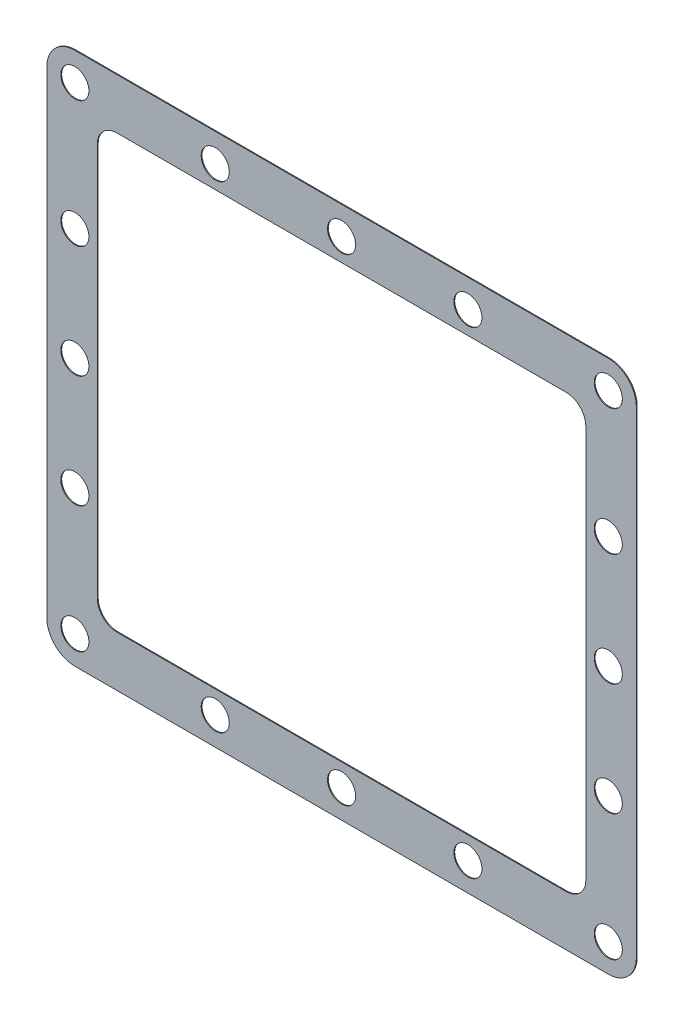
SolidWorks part; units mm, degrees
ref_plane "前视基准面" through (0, 0, 0) normal (0, 0, 1) x (1, 0, 0)
ref_plane "上视基准面" through (0, 0, 0) normal (0, 1, 0) x (1, 0, 0)
ref_plane "右视基准面" through (0, 0, 0) normal (1, 0, 0) x (0, 0, -1)
sketch "草图1" plane through (0, 0, 0) normal (0, 0, 1) x (1, 0, 0)
  line L0 (95, -85) -> (95, 85) construction
  line L1 (-95, -95) -> (95, -95)
  line L2 (-105, -85) -> (-105, 85)
  line L3 (-95, 95) -> (95, 95)
  line L4 (105, -85) -> (105, 85)
  line L5 (-105, -95) -> (105, 95) construction
  line L6 (-105, 95) -> (105, -95) construction
  line L7 (-80, -77) -> (80, -77)
  line L8 (-87, -70) -> (-87, 70)
  line L9 (-80, 77) -> (80, 77)
  line L10 (87, -70) -> (87, 70)
  line L11 (-87, -77) -> (87, 77) construction
  line L12 (-87, 77) -> (87, -77) construction
  line L13 (0, 0) -> (0, 37.6622) construction
  line L14 (0, 0) -> (41.7484, 0) construction
  line L15 (-95, 85) -> (95, 85) construction
  line L16 (-95, -85) -> (95, -85) construction
  arc A0 (95, 95) -> (105, 85) centre (95, 85) cw
  arc A1 (95, -95) -> (105, -85) centre (95, -85) ccw
  arc A2 (-95, -95) -> (-105, -85) centre (-95, -85) cw
  arc A3 (-105, 85) -> (-95, 95) centre (-95, 85) cw
  arc A4 (80, 77) -> (87, 70) centre (80, 70) cw
  arc A5 (80, -77) -> (87, -70) centre (80, -70) ccw
  arc A6 (-80, -77) -> (-87, -70) centre (-80, -70) cw
  arc A7 (-87, 70) -> (-80, 77) centre (-80, 70) cw
  circle A8 centre (95, -85) radius 5
  circle A9 centre (95, 85) radius 5
  circle A10 centre (-95, 85) radius 5
  circle A11 centre (-95, -85) radius 5
  circle A12 centre (95, 0) radius 5
  circle A13 centre (95, -40) radius 5
  circle A14 centre (95, 40) radius 5
  circle A15 centre (-95, -40) radius 5
  circle A16 centre (-95, 0) radius 5
  circle A17 centre (-95, 40) radius 5
  circle A18 centre (0, 85) radius 5
  circle A19 centre (-45, 85) radius 5
  circle A20 centre (45, 85) radius 5
  circle A21 centre (0, -85) radius 5
  circle A22 centre (-45, -85) radius 5
  circle A23 centre (45, -85) radius 5
  point P0 (0, 0)
  point P18 (0, 0)
  dimension "D3" = 10
  dimension "D6" = 7
  dimension "D7" = 10
  dimension "D8" = 10
  dimension "D9" = 10
  dimension "D10" = 10
  dimension "D11" = 10
  dimension "D12" = 10
  dimension "D13" = 10
  dimension "D14" = 40
  dimension "D15" = 40
  dimension "D16" = 10
  dimension "D17" = 10
  dimension "D18" = 10
  dimension "D19" = 45
  dimension "D20" = 45
  dimension "D21" = 10
  dimension "D22" = 10
  dimension "D23" = 45
  dimension "D24" = 45
  dimension "D25" = 10
  dimension "D1" = 190
  dimension "D2" = 210
  dimension "D4" = 18
  dimension "D5" = 18
extrude "凸台-拉伸1" add sketch "草图1" along normal blind 0.3
